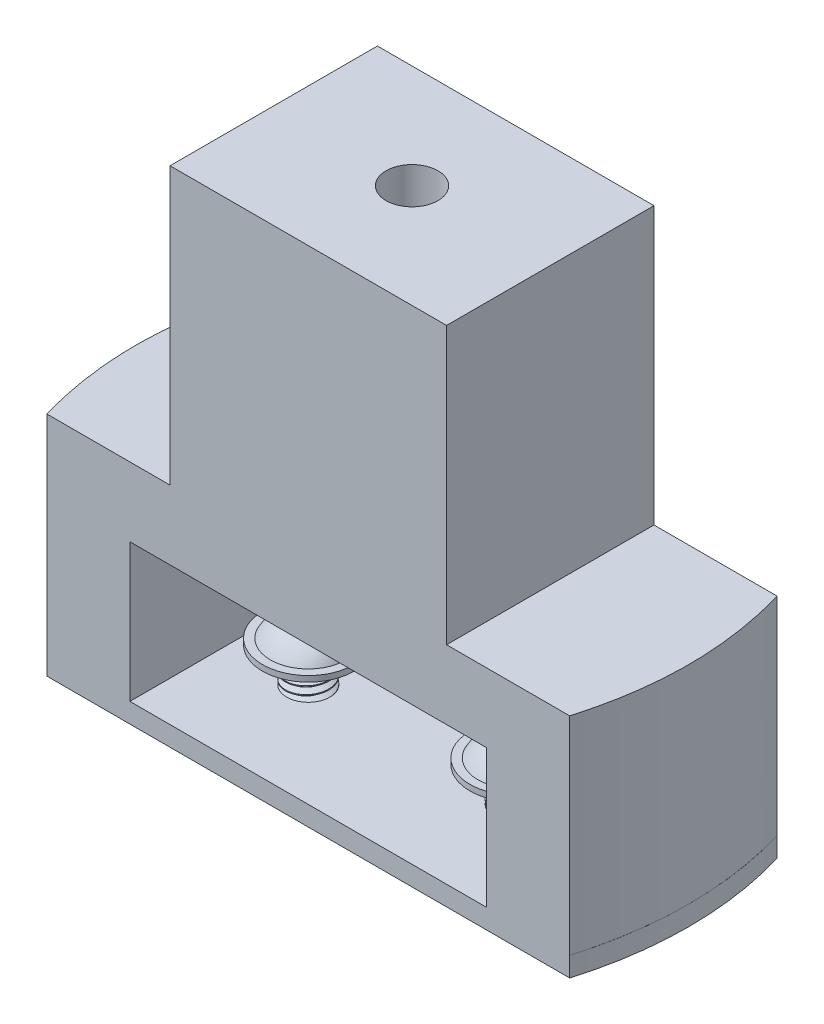
SolidWorks part; units mm, degrees
ref_plane "Front Plane" through (0, 0, 0) normal (0, 0, 1) x (1, 0, 0)
ref_plane "Top Plane" through (0, 0, 0) normal (0, 1, 0) x (1, 0, 0)
ref_plane "Right Plane" through (0, 0, 0) normal (1, 0, 0) x (0, 0, -1)
sketch "Sketch1" plane through (0, 0, 0) normal (0, 1, 0) x (1, 0, 0)
  line L0 (-19.05, 0) -> (19.05, 0) construction
  circle A0 centre (-19.05, 0) radius 3.9688
  point P3 (-23.0188, 0)
  point P4 (-15.0813, 0)
  dimension "D1" = 7.9375
  dimension "D2" = 38.1
extrude "Boss-Extrude1" add sketch "Sketch1" against normal blind 17.4625
sketch "Sketch2" plane through (0, -17.4625, 0) normal (0, -1, 0) x (1, 0, 0)
  circle A1 centre (-19.05, 0) radius 3.9688
  circle A2 centre (-19.05, 0) radius 3.9688
  point P0 (-19.05, -3.9688)
  dimension "D1" = 0
curve "Helix/Spiral1" pitch 1.4111 height 18.8736 turns 13.375
ref_plane "Plane1" through (-19.05, 0, 0) normal (1, 0, 0) x (0, 0, -1)
sketch "Sketch3" plane through (-19.05, 0, 0) normal (1, 0, 0) x (0, 0, -1)
  line L0 (4.1215, -17.3743) -> (2.8994, -18.0799) construction
  line L1 (2.8994, -18.0799) -> (4.1215, -18.7854) construction
  line L2 (4.1215, -18.7854) -> (4.1215, -17.3743) construction
  line L3 (3.0522, -17.9917) -> (3.0522, -18.1681) construction
  line L4 (3.9688, -17.4625) -> (3.9688, -18.6972) construction
  line L5 (2.8994, -18.0799) -> (3.0522, -18.0799) construction
  line L6 (3.9688, -18.0799) -> (4.1215, -18.0799) construction
  line L8 (2.8994, -18.0799) -> (-3.9688, -18.0799) construction
  line L9 (3.0522, -17.9917) -> (4.0451, -17.4184)
  line L10 (3.0522, -17.9917) -> (3.0522, -18.1681)
  line L11 (3.0522, -18.1681) -> (4.0451, -18.7413)
  line L12 (4.0451, -18.7413) -> (4.0451, -17.4184)
  line L14 (-3.9688, -18.0799) -> (-3.9688, -16.6687) construction
  line L15 (-3.9688, -16.6687) -> (-3.9688, -15.2576) construction
  line L16 (-3.9688, -15.2576) -> (-3.9687, -13.8465) construction
  line L17 (-3.9687, -13.8465) -> (-3.9688, -12.4354) construction
  line L18 (-3.9688, 0) -> (-3.9688, -17.4625) construction
  point P15 (4.0451, -18.0799)
  dimension "D1" = 1.4111
  dimension "D2" = 0.1764
sweep "Cut-Sweep1" cut profiles "Sketch3" path "Helix/Spiral1" align with end faces yes
sketch "Sketch4" plane through (0, -17.4625, 0) normal (0, -1, 0) x (1, 0, 0)
  circle A0 centre (-19.05, 0) radius 2.8994
extrude "Cut-Extrude1" cut sketch "Sketch4" against normal blind 1.4111 draft 45 flip side to cut
sketch "Sketch5" plane through (0, 0, 0) normal (0, 0, 1) x (1, 0, 0)
  line L0 (-19.05, 0) -> (-19.05, 4.2164)
  line L1 (-27.4701, 0) -> (-19.05, 0)
  line L2 (-19.05, 4.2164) -> (-23.0188, 4.2164)
  line L3 (-25.9969, 1.0541) -> (-27.4701, 1.0541)
  line L4 (-27.4701, 1.0541) -> (-27.4701, 0)
  line L5 (-19.05, 0) -> (-19.05, -17.4625) construction
  arc A0 (-23.0188, 4.2164) -> (-25.9969, 1.0541) centre (-19.05, -2.5047) ccw
  dimension "D1" = 4.2164
  dimension "D2" = 1.0541
  dimension "D3" = 16.8402
  dimension "D4" = 13.8938
revolve "Revolve1" add sketch "Sketch5" angle 360 mid plane about L0
sketch "Sketch6" plane through (0, 4.2164, 0) normal (0, 1, 0) x (1, 0, 0)
  line L1 (-19.05, 2.7496) -> (-21.4313, 1.3748)
  line L2 (-21.4313, 1.3748) -> (-21.4312, -1.3748)
  line L3 (-21.4312, -1.3748) -> (-19.05, -2.7496)
  line L4 (-19.05, -2.7496) -> (-16.6688, -1.3748)
  line L5 (-16.6688, -1.3748) -> (-16.6688, 1.3748)
  line L6 (-16.6688, 1.3748) -> (-19.05, 2.7496)
  circle A0 centre (-19.05, 0) radius 2.3813 construction
  dimension "D1" = 4.7625
extrude "Cut-Extrude2" cut sketch "Sketch6" against normal blind 2.8575
sketch "Sketch7" plane through (0, 4.2164, 0) normal (0, 1, 0) x (1, 0, 0)
  circle A0 centre (-19.05, 0) radius 2.7496
extrude "Cut-Extrude3" cut sketch "Sketch7" against normal blind 2.8575 draft 45
move or copy body "Body-Move/Copy1" bodies to move or copy 110 copy yes number of copies 1 translate (38.1, 0, 0)
sketch "Sketch8" plane through (0, 0, 0) normal (0, 1, 0) x (1, 0, 0)
  line L0 (-50.8, 0) -> (50.8, 0) construction
  line L2 (-48.0139, 19.05) -> (48.0139, 19.05)
  line L3 (-48.0139, -19.05) -> (48.0139, -19.05)
  line L4 (-50.8, 19.05) -> (50.8, 19.05) construction
  line L5 (-50.8, 19.05) -> (-50.8, -19.05) construction
  line L6 (-50.8, -19.05) -> (50.8, -19.05) construction
  line L7 (50.8, 19.05) -> (50.8, -19.05) construction
  arc A0 (-48.0139, 19.05) -> (-48.0139, -19.05) centre (15.7212, 0) ccw
  arc A1 (48.0139, 19.05) -> (48.0139, -19.05) centre (-15.7212, 0) cw
  circle A2 centre (19.05, 0) radius 3.9688
  circle A3 centre (-19.05, 0) radius 3.9688
  circle A4 centre (-19.05, 0) radius 3.9688
  dimension "D2" = 101.6
  dimension "D3" = 38.1
  dimension "D4" = 31.75
  dimension "D1" = 0
extrude "Boss-Extrude2" add sketch "Sketch8" against normal blind 3.6068 from offset 6.35 separate body offset against normal yes
sketch "Sketch10" plane through (0, -6.35, 0) normal (0, 1, 0) x (1, 0, 0)
  line L0 (-48.0139, 19.05) -> (-32.7739, 19.05)
  line L1 (48.0139, 19.05) -> (-48.0139, 19.05) construction
  line L2 (-32.7739, 19.05) -> (-32.7739, -19.05)
  line L3 (-48.0139, -19.05) -> (48.0139, -19.05) construction
  line L4 (-32.7739, -19.05) -> (-48.0139, -19.05)
  line L5 (48.0139, 19.05) -> (32.7739, 19.05)
  line L6 (32.7739, 19.05) -> (32.7739, -19.05)
  line L7 (32.7739, -19.05) -> (48.0139, -19.05)
  arc A0 (-48.0139, 19.05) -> (-48.0139, -19.05) centre (15.7212, 0) ccw construction
  arc A1 (48.0139, -19.05) -> (48.0139, 19.05) centre (-15.7212, 0) ccw construction
  spline S0 degree 2 poles (-48.0139, 19.05) (-53.5861, 0) (-48.0139, -19.05) knots 0 0 0 1 1 1
  spline S1 degree 2 poles (48.0139, -19.05) (53.5861, 0) (48.0139, 19.05) knots 0 0 0 1 1 1
extrude "Boss-Extrude4" add sketch "Sketch10" along normal blind 25.4
sketch "Sketch11" plane through (0, 19.05, 0) normal (0, 1, 0) x (1, 0, 0)
  line L0 (-48.0139, 19.05) -> (48.0139, 19.05)
  line L1 (48.0139, -19.05) -> (-48.0139, -19.05)
  parabola Q0 (-48.0139, 19.05) -> (-48.0139, -19.05) focus (-18.2359, 0) apex (-50.8, 0) construction
  parabola Q1 (-48.0139, 19.05) -> (-50.8, 0) focus (-18.2359, 0) apex (-50.8, 0) construction
  spline S0 degree 2 poles (-48.0139, 19.05) (-53.5861, 0) (-48.0139, -19.05) knots 0 0 0 1 1 1
  spline S1 degree 2 poles (48.0139, 19.05) (53.5861, 0) (48.0139, -19.05) knots 0 0 0 1 1 1
extrude "Boss-Extrude5" add sketch "Sketch11" along normal blind 12.7
sketch "Sketch12" plane through (0, 31.75, 0) normal (0, 1, 0) x (1, 0, 0)
  line L0 (0, 19.05) -> (25.4, 19.05)
  line L1 (48.0139, 19.05) -> (-48.0139, 19.05) construction
  line L2 (25.4, 19.05) -> (25.4, -19.05)
  line L3 (-48.0139, -19.05) -> (48.0139, -19.05) construction
  line L4 (25.4, -19.05) -> (-25.4, -19.05)
  line L5 (-25.4, -19.05) -> (-25.4, 19.05)
  line L6 (-25.4, 19.05) -> (0, 19.05)
extrude "Boss-Extrude6" add sketch "Sketch12" along normal blind 50.8
sketch "Sketch13" plane through (0, 0, 19.05) normal (0, 0, 1) x (1, 0, 0)
  line L0 (-25.4, 82.55) -> (25.4, 82.55)
  line L1 (25.4, 82.55) -> (25.4, 31.75)
  line L2 (25.4, 31.75) -> (-25.4, 31.75)
  line L3 (-25.4, 31.75) -> (-25.4, 82.55)
sketch "Sketch9" plane through (0, -9.9568, 0) normal (0, -1, 0) x (1, 0, 0)
  circle A0 centre (19.05, 0) radius 3.9688 construction
  circle A1 centre (-19.05, 0) radius 3.9688 construction
  circle A2 centre (-19.05, 0) radius 3.9688
  circle A3 centre (-19.05, 0) radius 4.5593
  circle A4 centre (19.05, 0) radius 3.9688
  circle A5 centre (19.05, 0) radius 4.5593
  dimension "D1" = 9.1186
extrude "Boss-Extrude3" add sketch "Sketch9" along normal blind 2.032
sketch "Sketch14" plane through (0, 82.55, 0) normal (0, 1, 0) x (1, 0, 0)
  circle A0 centre (0, 0) radius 4.7625
extrude "Cut-Extrude4" cut sketch "Sketch14" against normal blind 38.1
sketch "SketchZ" plane through (0, 0, 0) normal (0, 0, 1) x (1, 0, 0)
  line L0 (-15.0813, -17.7271) -> (-15.0813, -16.316) construction
  line L2 (-19.05, -18.0799) -> (-19.05, -16.6687) construction
  line L4 (-15.0813, -17.7271) -> (-19.05, -17.7271) construction
  line L5 (-19.05, -13.8465) -> (-19.05, -12.4354) construction
  line L6 (-19.05, -17.3743) -> (-19.05, -18.0799) construction
equation "\"D3@Helix/Spiral1\" = \"D4@Helix/Spiral1\" + \"D1@Boss-Extrude1\""
equation "\"D1@Sketch3\" = \"D4@Helix/Spiral1\""
equation "\"D2@Sketch3\" = \"D1@Sketch3\" / 8"
equation "\"D1@Cut-Extrude1\" = \"D4@Helix/Spiral1\""
equation "\"D1@Cut-Extrude2\" = \"D1@Sketch6\" * 3/5"
equation "\"D1@Cut-Extrude3\" = \"D1@Cut-Extrude2\""
equation "\"D2@Sketch5\" = \"D1@Sketch5\" * 1/4"
